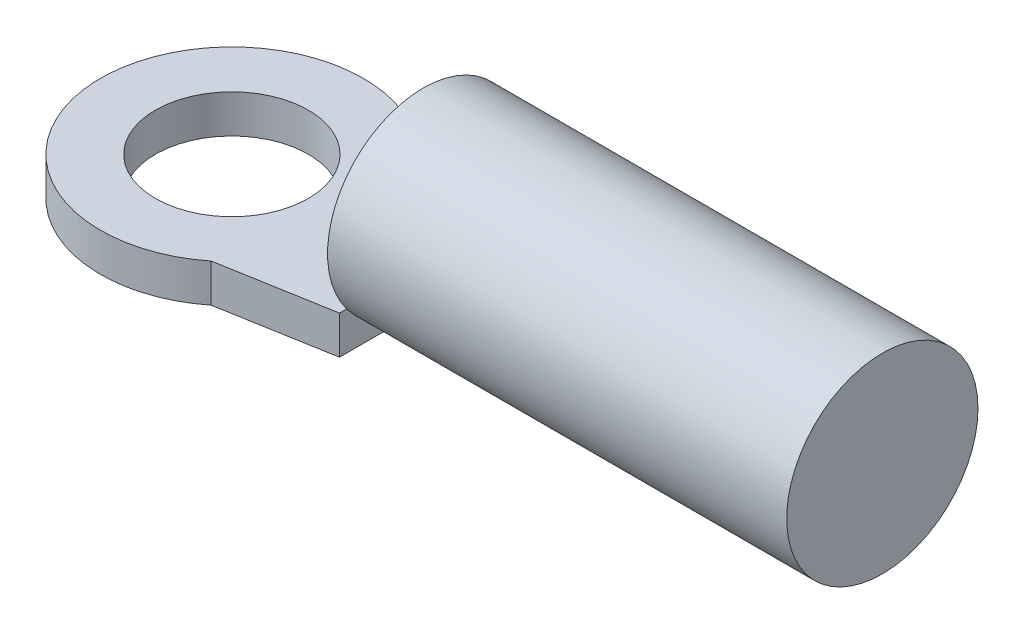
SolidWorks part; units mm, degrees
material "acero"
ref_plane "Alzado" through (0, 0, 0) normal (0, 0, 1) x (1, 0, 0)
ref_plane "Planta" through (0, 0, 0) normal (0, 1, 0) x (1, 0, 0)
ref_plane "Vista lateral" through (0, 0, 0) normal (1, 0, 0) x (0, 0, -1)
sketch "Sketch1" plane through (0, 0, 0) normal (0, 1, 0) x (1, 0, 0)
  line L0 (0, 0) -> (4, 0) construction
  line L1 (4, 1.75) -> (4, -1.75)
  line L2 (4, 1.75) -> (1.7146, 2.15)
  line L3 (4, -1.75) -> (1.7146, -2.15)
  circle A0 centre (0, 0) radius 1.6
  circle A1 centre (0, 0) radius 2.75
  point P7 (4, 0)
  dimension "D1" = 3.2
  dimension "D2" = 5.5
  dimension "D3" = 4
  dimension "D4" = 3.5
  dimension "D5" = 4.3
extrude "Boss-Extrude1" add sketch "Sketch1" along normal blind 0.8 contours A0 A1 | L0 A1 L3 L1 | A1 L0 L1 L2 region at (2.4076, 0, 1.1594) region at (3.1822, 0, -1.057) region at (3.1822, 0, 1.057)
sketch "Sketch2" plane through (4, 0, 0) normal (1, 0, 0) x (0, 0, -1)
  line L0 (0, 0) -> (0, 2) construction
  line L1 (1.75, 0) -> (-1.75, 0) construction
  circle A0 centre (0, 2) radius 2
  dimension "D1" = 4
extrude "Boss-Extrude2" add sketch "Sketch2" along normal blind 9.6
ref_plane "Plano1" through (13.6, 0, 0) normal (1, 0, 0) x (0, 0, -1)
sketch "Croquis1" plane through (13.6, 0, 0) normal (1, 0, 0) x (0, 0, -1)
  point P0 (0, 2)
other "PuntoC2" parameters "Diámetro"=1.75, "Longitud de terminal"=2.625
ref_axis "Eje2" through (23.6, 2, 0) along (-1, 0, 0)
